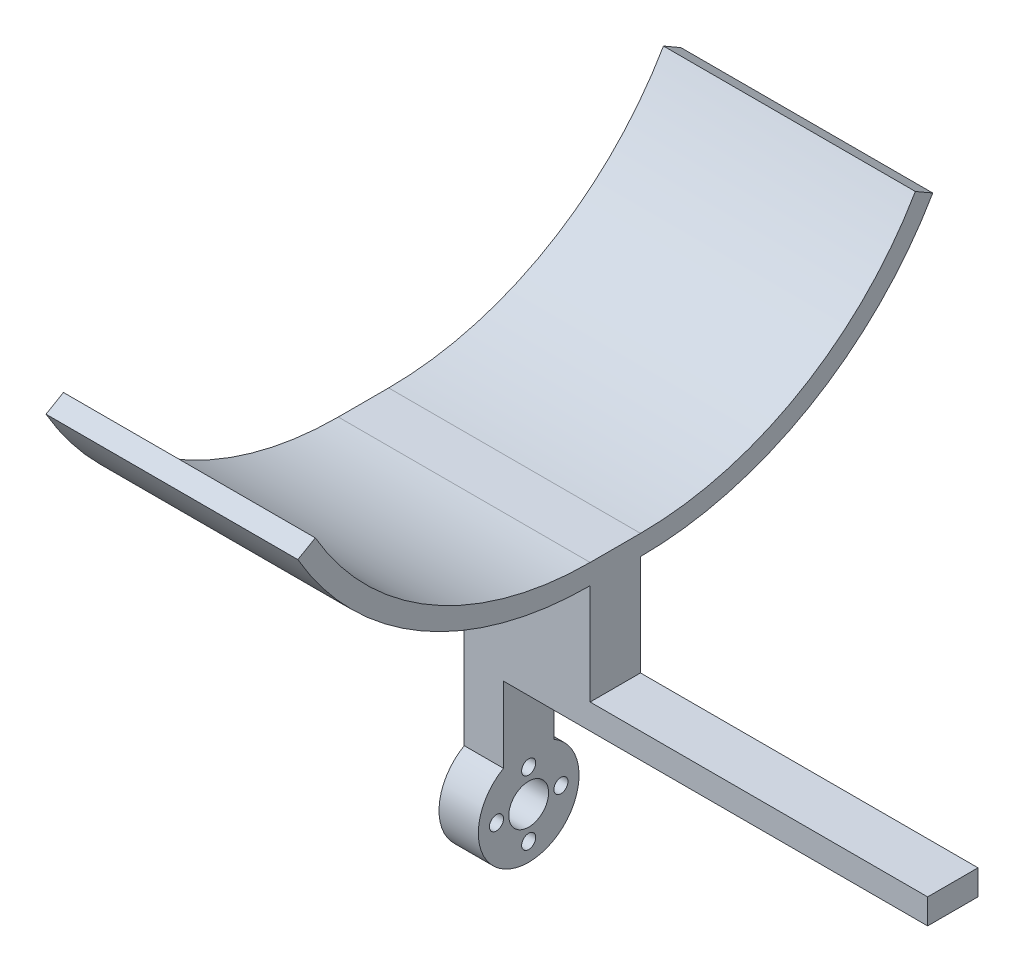
SolidWorks part; units mm, degrees
ref_plane "Front Plane" through (0, 0, 0) normal (0, 0, 1) x (1, 0, 0)
ref_plane "Top Plane" through (0, 0, 0) normal (0, 1, 0) x (1, 0, 0)
ref_plane "Right Plane" through (0, 0, 0) normal (1, 0, 0) x (0, 0, -1)
sketch "Sketch1" plane through (0, 0, 0) normal (1, 0, 0) x (0, 0, -1)
  line L0 (0, 0) -> (-27.0167, 0) construction
  line L2 (-6.35, 10.9985) -> (-6.35, 61.7985)
  line L3 (-6.35, 61.7985) -> (6.35, 61.7985)
  line L4 (6.35, 10.9985) -> (6.35, 61.7985)
  line L5 (0, 0) -> (12.7, 0) construction
  line L6 (-27.0167, 0) -> (-27.0167, 61.7985) construction
  line L7 (-6.35, 61.7985) -> (-27.0167, 61.7985) construction
  circle A0 centre (0, 0) radius 5.0165
  arc A1 (-6.35, 10.9985) -> (6.35, 10.9985) centre (0, 0) ccw
  circle A2 centre (-8.128, 0) radius 1.778
  circle A12 centre (0, -8.128) radius 1.778 [skipped]
  circle A13 centre (0, 8.128) radius 1.778 [skipped]
  circle A14 centre (8.128, 0) radius 1.778 [skipped]
  circle A15 centre (8.128, 0) radius 1.778
  circle A16 centre (0, -8.128) radius 1.778
  circle A17 centre (0, 8.128) radius 1.778
  point P0 (0, 0)
  point P16 (0, 0)
  point P19 (0, 0)
  point P22 (0, -45.974)
  point P23 (0, 11.6075)
  point P24 (0, 0)
  point P27 (0, 0)
  dimension "D3" = 10.033
  dimension "D4" = 25.4
  dimension "D5" = 50.8
  dimension "D1" = 3.556
  dimension "D8" = 3.556
  dimension "D10" = 3.556
  dimension "D11" = 3.556
  dimension "D2" = 12.7
  dimension "D6" = 8.128
  dimension "D9" = 8.128
  dimension "D12" = 8.128
  dimension "D13" = 8.128
  dimension "D7" = 4
extrude "Boss-Extrude1" add sketch "Sketch1" along normal blind 9.906
sketch "Sketch3" plane through (0, 0, 0) normal (1, 0, 0) x (0, 0, -1)
  line L0 (0, 61.7985) -> (0, 315.7985) construction
  line L1 (6.35, 61.7985) -> (-6.35, 61.7985) construction
  line L2 (0, 55) -> (0, -55) construction
  line L5 (0, 61.7985) -> (0, 66.8785)
  line L12 (-6.35, 61.7985) -> (-6.35, 146.8885) construction
  line L13 (6.35, 61.7985) -> (6.35, 146.8885) construction
  line L14 (6.35, 10.9985) -> (6.35, 61.7985) construction
  line L15 (-80.0401, 104.3435) -> (-75.6407, 106.8835)
  line L18 (-6.35, 66.8785) -> (6.35, 66.8785)
  line L19 (6.35, 61.7985) -> (-6.35, 61.7985)
  line L20 (6.35, 146.8885) -> (100.7099, 92.4098) construction
  line L21 (0, 61.7985) -> (91.44, 61.7985) construction
  line L22 (-6.35, 146.8885) -> (-92.0925, 97.385) construction
  line L23 (80.0401, 104.3435) -> (75.6407, 106.8835)
  arc A1 (-80.0401, 104.3435) -> (-6.35, 61.7985) centre (-6.35, 146.8885) ccw
  arc A2 (6.35, 61.7985) -> (80.0401, 104.3435) centre (6.35, 146.8885) ccw
  arc A3 (-75.6407, 106.8835) -> (-6.35, 66.8785) centre (-6.35, 146.8885) ccw
  arc A5 (6.35, 66.8785) -> (75.6407, 106.8835) centre (6.35, 146.8885) ccw
  dimension "D1" = 85.09
  dimension "D3" = 85.09
  dimension "D2" = 5.08
extrude "Boss-Extrude2" add sketch "Sketch3" along normal blind 31.75 and the other way blind 31.75 contours L5 | L5 region at (0, 62.7172, 3.175) region at (0, 64.3385, -0.9186)
sketch "Sketch4" plane through (0, 0, 0) normal (-1, 0, 0) x (0, 0, 1)
  line L0 (0, 12.7) -> (0, 53.747) construction
  line L1 (0, -34.925) -> (0, 34.925) construction
  line L2 (6.35, 61.7985) -> (6.35, 10.9985) construction
  line L3 (-6.35, 30.0485) -> (6.35, 30.0485)
  line L4 (-6.35, 30.0485) -> (-6.35, 36.3985)
  line L5 (-6.35, 36.3985) -> (6.35, 36.3985)
  line L6 (6.35, 30.0485) -> (6.35, 36.3985)
  line L7 (-6.35, 30.0485) -> (6.35, 36.3985) construction
  line L8 (-6.35, 36.3985) -> (6.35, 30.0485) construction
  line L9 (0, 36.3985) -> (19.9669, 36.3985) construction
  circle A0 centre (0, 0) radius 12.7 construction
  point P9 (0, 33.2235)
  dimension "D1" = 6.35
extrude "Boss-Extrude3" add sketch "Sketch4" against normal blind 106.934 from offset 9.906 offset against normal yes
sketch "Sketch5" plane through (9.906, 0, 0) normal (1, 0, 0) x (0, 0, -1)
  line L1 (-6.35, 36.3985) -> (6.35, 36.3985)
  line L2 (-6.35, 36.3985) -> (-6.35, 61.7985)
  line L3 (-6.35, 61.7985) -> (6.35, 61.7985)
  line L4 (6.35, 36.3985) -> (6.35, 61.7985)
extrude "Boss-Extrude4" add sketch "Sketch5" along normal up to surface (21.844 mm away) and the other way up to surface (41.656 mm away) up to face at (31.75, 80.1871, 0) other way up to face at (-31.75, 80.1871, 0)
